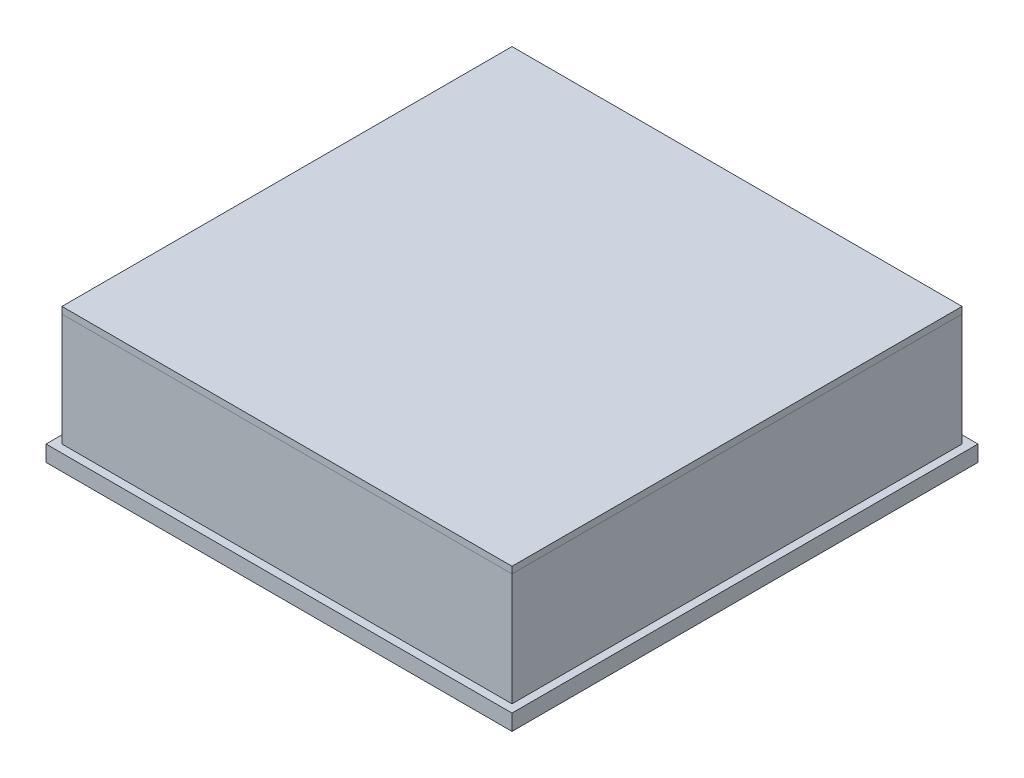
SolidWorks part; units mm, degrees
ref_plane "Front Plane" through (0, 0, 0) normal (0, 0, 1) x (1, 0, 0)
ref_plane "Top Plane" through (0, 0, 0) normal (0, 1, 0) x (1, 0, 0)
ref_plane "Right Plane" through (0, 0, 0) normal (1, 0, 0) x (0, 0, -1)
sketch "Sketch2" plane through (0, 0, 0) normal (0, 1, 0) x (1, 0, 0)
  line L0 (-4304.792, -4304.792) -> (-4304.792, 4304.792)
  line L1 (3999.992, -3999.992) -> (-3999.992, -3999.992)
  line L2 (3999.992, -3999.992) -> (3999.992, 3999.992)
  line L3 (3999.992, 3999.992) -> (-3999.992, 3999.992)
  line L4 (-3999.992, -3999.992) -> (-3999.992, 3999.992)
  line L5 (3999.992, -3999.992) -> (-3999.992, 3999.992) construction
  line L6 (3999.992, 3999.992) -> (-3999.992, -3999.992) construction
  line L7 (4304.792, 4304.792) -> (-4304.792, 4304.792)
  line L8 (4304.792, -4304.792) -> (4304.792, 4304.792)
  line L9 (4304.792, -4304.792) -> (-4304.792, -4304.792)
  point P0 (0, 0)
  dimension "D1" = 7999.984
  dimension "D2" = 7999.984
  dimension "D3" = 304.8
extrude "Boss-Extrude1" add sketch "Sketch2" along normal blind 1999.996
sketch "Sketch3" plane through (0, 0, 0) normal (0, -1, 0) x (1, 0, 0)
  line L0 (-4304.792, -4304.792) -> (-4304.792, 4304.792) construction
  line L1 (-4304.792, -4304.792) -> (-4304.792, 4304.792)
  line L2 (4304.792, -4304.792) -> (-4304.792, -4304.792) construction
  line L3 (4304.792, 4304.792) -> (4304.792, -4304.792) construction
  line L4 (-4304.792, 4304.792) -> (4304.792, 4304.792) construction
  line L5 (4304.792, -4304.792) -> (-4304.792, -4304.792)
  line L6 (4304.792, 4304.792) -> (4304.792, -4304.792)
  line L7 (-4304.792, 4304.792) -> (4304.792, 4304.792)
extrude "Boss-Extrude2" add sketch "Sketch3" along normal blind 152.4
sketch "Sketch4" plane through (0, -152.4, 0) normal (0, -1, 0) x (1, 0, 0)
  line L30 (-4457.192, 4457.192) -> (-4457.192, -4457.192)
  line L31 (-4457.192, -4457.192) -> (4457.192, -4457.192)
  line L32 (4457.192, -4457.192) -> (4457.192, 4457.192)
  line L33 (4457.192, 4457.192) -> (-4457.192, 4457.192)
  line L34 (-4457.192, 4457.192) -> (-4457.192, -4457.192)
  line L35 (-4457.192, -4457.192) -> (4457.192, -4457.192)
  line L36 (4457.192, -4457.192) -> (4457.192, 4457.192)
  line L37 (4457.192, 4457.192) -> (-4457.192, 4457.192)
  line L43 (3847.592, 3847.592) -> (-3847.592, 3847.592)
  line L44 (-3847.592, 3847.592) -> (-3847.592, -3847.592)
  line L45 (-3847.592, -3847.592) -> (3847.592, -3847.592)
  line L46 (3847.592, -3847.592) -> (3847.592, 3847.592)
  line L47 (3847.592, 3847.592) -> (-3847.592, 3847.592)
  line L48 (-3847.592, 3847.592) -> (-3847.592, -3847.592)
  line L49 (-3847.592, -3847.592) -> (3847.592, -3847.592)
  line L50 (3847.592, -3847.592) -> (3847.592, 3847.592)
  dimension "D1" = 152.4
  dimension "D2" = 152.4
extrude "Boss-Extrude3" add sketch "Sketch4" along normal blind 304.8
sketch "Sketch6" plane through (0, 0, 0) normal (0, 1, 0) x (1, 0, 0)
  line L0 (0, 0) -> (-3999.992, 3999.992) construction
  line L6 (-3999.992, 1656.8509) -> (-1656.8509, 1656.8509) construction
  line L7 (-3999.992, 3999.992) -> (-3999.992, -3999.992) construction
  line L19 (-1656.8509, 1656.8509) -> (-1656.8509, 3999.992) construction
  line L20 (3999.992, 3999.992) -> (-3999.992, 3999.992) construction
  line L22 (-1656.8509, 1656.8509) -> (0, 0) construction
  line L24 (1809.2509, 1504.4509) -> (1809.2509, 1809.2509)
  line L25 (-1504.4509, 1809.2509) -> (-1809.2509, 1809.2509)
  line L29 (-1504.4509, 1809.2509) -> (-1504.4509, 1504.4509)
  line L30 (-1504.4509, 1504.4509) -> (-1809.2509, 1504.4509)
  line L31 (-1809.2509, 1809.2509) -> (-1809.2509, 1504.4509)
  line L32 (-1504.4509, 1809.2509) -> (-1809.2509, 1504.4509) construction
  line L33 (-1504.4509, 1504.4509) -> (-1809.2509, 1809.2509) construction
  line L34 (1809.2509, 1809.2509) -> (1504.4509, 1809.2509)
  line L35 (1504.4509, 1504.4509) -> (1504.4509, 1809.2509)
  line L36 (1809.2509, 1504.4509) -> (1504.4509, 1504.4509)
  line L37 (1504.4509, -1809.2509) -> (1809.2509, -1809.2509)
  line L38 (1809.2509, -1809.2509) -> (1809.2509, -1504.4509)
  line L39 (1504.4509, -1504.4509) -> (1809.2509, -1504.4509)
  line L40 (1504.4509, -1809.2509) -> (1504.4509, -1504.4509)
  line L41 (-1809.2509, -1504.4509) -> (-1809.2509, -1809.2509)
  line L42 (-1809.2509, -1809.2509) -> (-1504.4509, -1809.2509)
  line L43 (-1504.4509, -1504.4509) -> (-1504.4509, -1809.2509)
  line L44 (-1809.2509, -1504.4509) -> (-1504.4509, -1504.4509)
  point P30 (0, 0)
  dimension "D1" = 304.8
extrude "Boss-Extrude5" add sketch "Sketch6" along normal up to surface (1999.996 mm away) contours L25 L31 L30 L29 | L36 L24 L34 L35 | L40 L37 L38 L39 | L44 L41 L42 L43 region at (1656.8509, 0, -1656.8509) region at (-1656.8509, 0, -1656.8509) region at (1656.8509, 0, 1656.8509) region at (-1656.8509, 0, 1656.8509) up to face at (0, 1999.996, 0)
sketch "Sketch7" plane through (0, 1999.996, 0) normal (0, 1, 0) x (1, 0, 0)
  line L1 (4304.792, -4304.792) -> (-4304.792, -4304.792)
  line L2 (4304.792, -4304.792) -> (4304.792, 4304.792)
  line L3 (4304.792, 4304.792) -> (-4304.792, 4304.792)
  line L4 (-4304.792, -4304.792) -> (-4304.792, 4304.792)
  line L5 (4304.792, -4304.792) -> (-4304.792, 4304.792) construction
  line L6 (4304.792, 4304.792) -> (-4304.792, -4304.792) construction
  point P0 (0, 0)
extrude "Boss-Extrude6" add sketch "Sketch7" along normal blind 127 separate body
sketch "Sketch8" plane through (0, 0, -1504.4509) normal (0, 0, 1) x (1, 0, 0)
  line L0 (-3999.992, 1999.996) -> (-3999.992, 0) construction
  line L1 (3999.992, 1999.996) -> (-3999.992, 1999.996)
  line L2 (3999.992, 1999.996) -> (3999.992, 1753.1524)
  line L3 (3999.992, 1753.1524) -> (-3999.992, 1753.1524)
  line L4 (-3999.992, 1999.996) -> (-3999.992, 1753.1524)
  line L5 (3999.992, 1999.996) -> (-3999.992, 1753.1524) construction
  line L6 (3999.992, 1753.1524) -> (-3999.992, 1999.996) construction
  line L7 (3999.992, 1999.996) -> (-3999.992, 1999.996) construction
  line L8 (3999.992, 1999.996) -> (-3999.992, 1999.996)
  point P0 (0, 1876.5742)
ref_axis "Axis1" through (0, 0, 0) along (0, 1, 0)
sketch "Right Plane Rebar" plane through (0, 0, 0) normal (1, 0, 0) x (0, 0, -1)
  line L0 (4234.942, 2063.496) -> (4234.942, -393.7)
  line L1 (-4457.192, -457.2) -> (4457.192, -457.2) construction
  line L2 (4069.842, 2044.446) -> (4069.842, 50.8)
  line L3 (4222.242, 1314.196) -> (4222.242, 1923.796)
  line L4 (-4304.792, 1999.996) -> (-4304.792, -152.4)
  line L5 (-4304.792, -152.4) -> (4304.792, -152.4)
  line L6 (4304.792, -152.4) -> (4304.792, 1999.996)
  line L7 (4304.792, 1999.996) -> (-4304.792, 1999.996)
  line L8 (-4304.792, 1999.996) -> (-4304.792, -152.4)
  line L9 (-4304.792, -152.4) -> (4304.792, -152.4)
  line L10 (4304.792, -152.4) -> (4304.792, 1999.996)
  line L12 (4095.242, 2050.796) -> (3485.642, 2050.796)
  line L13 (4095.242, 2063.496) -> (-4095.242, 2063.496)
  line L14 (0, 1351.4578) -> (0, -1351.4578) construction
  line L15 (3955.542, -88.9) -> (-3955.542, -88.9)
  line L16 (3999.992, 1999.996) -> (-3999.992, 1999.996)
  line L17 (3999.992, 1999.996) -> (-3999.992, 1999.996)
  line L18 (-4304.792, 2126.996) -> (4304.792, 2126.996) construction
  line L19 (3999.992, 0) -> (3999.992, 1999.996)
  line L20 (-3999.992, 0) -> (3999.992, 0)
  line L21 (-3999.992, 1999.996) -> (-3999.992, 0)
  line L27 (3999.992, 0) -> (3999.992, 1999.996)
  line L28 (-3999.992, 0) -> (3999.992, 0)
  line L29 (-3999.992, 1999.996) -> (-3999.992, 0)
  line L32 (4082.542, 660.4) -> (4082.542, 50.8)
  line L33 (3955.542, -76.2) -> (3345.942, -76.2)
  line L38 (4304.792, 1999.996) -> (-4304.792, 1999.996)
  arc A0 (4222.242, 1923.796) -> (4095.242, 2050.796) centre (4095.242, 1923.796) ccw
  arc A1 (3955.542, -76.2) -> (4082.542, 50.8) centre (3955.542, 50.8) ccw
  point P23 (4222.242, 2050.796)
  point P30 (0, 2063.496)
  point P41 (0, -88.9)
  dimension "D12" = 127
  dimension "D19" = 127
  dimension "D5" = 69.85
  dimension "Vertical Rebar Outer" = 2457.196
  dimension "D4" = 63.5
  dimension "D8" = 69.85
  dimension "D11" = 12.7
  dimension "D10" = 6.35
  dimension "D13" = 609.6
  dimension "D14" = 609.6
  dimension "D15" = 12.7
  dimension "D16" = 63.5
  dimension "D17" = 12.7
  dimension "D18" = 12.7
  dimension "D7" = 609.6
  dimension "D20" = 609.6
  dimension "Vertical Rebar Inner" = 1993.646
  dimension "Lid Rebar Length" = 8190.484
  dimension "Base Rebar Length" = 7911.084
  dimension "D3" = 63.5
  dimension "D6" = 63.5
sketch "Front Plane Rebar" plane through (0, 0, 0) normal (0, 0, 1) x (1, 0, 0)
  line L0 (4247.642, 2063.496) -> (4247.642, -393.7)
  line L1 (3999.992, 1999.996) -> (3999.992, 0) construction
  line L2 (4057.142, 2031.746) -> (4057.142, 63.5)
  line L3 (4234.942, 1301.496) -> (4234.942, 1911.096)
  line L4 (-4304.792, 2126.996) -> (4304.792, 2126.996) construction
  line L5 (4457.192, -457.2) -> (-4457.192, -457.2) construction
  line L6 (4457.192, -152.4) -> (-4457.192, -152.4) construction
  line L7 (4304.792, 2126.996) -> (-4304.792, 2126.996) construction
  line L8 (-4304.792, 1999.996) -> (-4304.792, -152.4)
  line L9 (-4304.792, -152.4) -> (4304.792, -152.4)
  line L10 (4304.792, -152.4) -> (4304.792, 1999.996)
  line L12 (4107.942, 2038.096) -> (3498.342, 2038.096)
  line L13 (4107.942, 2050.796) -> (-4107.942, 2050.796)
  line L15 (3942.842, -76.2) -> (-3942.842, -76.2)
  line L17 (3999.992, 1999.996) -> (-3999.992, 1999.996)
  line L19 (-3999.992, 0) -> (3999.992, 0)
  line L20 (3999.992, 0) -> (3999.992, 1999.996)
  line L21 (3999.992, 1999.996) -> (-3999.992, 1999.996)
  line L22 (-3999.992, 1999.996) -> (-3999.992, 0)
  line L23 (-3999.992, 0) -> (3999.992, 0)
  line L27 (3999.992, 0) -> (3999.992, 1999.996)
  line L28 (-3999.992, 0) -> (3999.992, 0)
  line L29 (-3999.992, 1999.996) -> (-3999.992, 0)
  line L32 (4069.842, 673.1) -> (4069.842, 63.5)
  line L33 (3942.842, -63.5) -> (3333.242, -63.5)
  line L34 (3999.992, 0) -> (3999.992, 1999.996)
  line L35 (3999.992, 1999.996) -> (-3999.992, 1999.996)
  line L36 (-3999.992, 1999.996) -> (-3999.992, 0)
  line L37 (4304.792, -152.4) -> (4304.792, 1999.996)
  line L38 (4304.792, 1999.996) -> (-4304.792, 1999.996)
  line L39 (-4304.792, -152.4) -> (4304.792, -152.4)
  line L40 (-4304.792, 1999.996) -> (-4304.792, -152.4)
  line L41 (4304.792, 1999.996) -> (-4304.792, 1999.996)
  line L42 (4304.792, -152.4) -> (4304.792, 1999.996)
  line L43 (-4304.792, -152.4) -> (4304.792, -152.4)
  line L44 (-4304.792, 1999.996) -> (-4304.792, -152.4)
  line L45 (4304.792, 1999.996) -> (-4304.792, 1999.996)
  arc A0 (4234.942, 1911.096) -> (4107.942, 2038.096) centre (4107.942, 1911.096) ccw
  arc A1 (3942.842, -63.5) -> (4069.842, 63.5) centre (3942.842, 63.5) ccw
  point P23 (4234.942, 2038.096)
  point P30 (0, 2050.796)
  point P41 (0, -76.2)
  dimension "D12" = 127
  dimension "D19" = 127
  dimension "Vertical Rebar Outer" = 2457.196
  dimension "D4" = 63.5
  dimension "D11" = 12.7
  dimension "D10" = 6.35
  dimension "D13" = 609.6
  dimension "D14" = 609.6
  dimension "D15" = 12.7
  dimension "D17" = 12.7
  dimension "D18" = 12.7
  dimension "D7" = 609.6
  dimension "D20" = 609.6
  dimension "D5" = 57.15
  dimension "D8" = 57.15
  dimension "D16" = 76.2
  dimension "Vertical Rebar Inner" = 1968.246
  dimension "Lid Rebar Length" = 8215.884
  dimension "Base Rebar Length" = 7885.684
  dimension "D3" = 76.2
  dimension "D21" = 63.5
sketch "Sketch9" plane through (0, -152.4, 0) normal (0, 1, 0) x (1, 0, 0)
  line L0 (-4260.342, 4393.692) -> (-4260.342, -4393.692)
  line L1 (-4457.192, -4457.192) -> (-4457.192, 4457.192) construction
  line L2 (-4457.192, -4457.192) -> (-4457.192, 4457.192)
  line L3 (-3847.592, -3847.592) -> (-3847.592, 3847.592) construction
  line L4 (-3847.592, -3847.592) -> (-3847.592, 3847.592)
  line L5 (-4457.192, 4457.192) -> (4457.192, 4457.192) construction
  line L6 (4457.192, -4457.192) -> (-4457.192, -4457.192) construction
  line L7 (-4044.442, 4152.392) -> (-4044.442, -4152.392)
  line L8 (4393.692, 4260.342) -> (-4393.692, 4260.342)
  line L9 (4152.392, 4044.442) -> (-4152.392, 4044.442)
  line L10 (4260.342, -4393.692) -> (4260.342, 4393.692)
  line L11 (4044.442, -4152.392) -> (4044.442, 4152.392)
  line L12 (-4393.692, -4260.342) -> (4393.692, -4260.342)
  line L13 (-4152.392, -4044.442) -> (4152.392, -4044.442)
  point P27 (0, 0)
  dimension "D3" = 63.5
  dimension "D1" = 196.85
  dimension "D2" = 63.5
  dimension "D4" = 196.85
  dimension "D5" = 304.8
  dimension "D6" = 304.8
  dimension "D7" = 8787.384
  dimension "D8" = 8304.784
  dimension "D9" = 4
sketch "Sketch11" plane through (0, 0, -1504.4509) normal (0, 0, 1) x (1, 0, 0)
  line L0 (-1745.7509, 2063.496) -> (-1745.7509, -88.9)
  line L1 (-1745.7509, 2063.496) -> (-1745.7509, 1930.146)
  line L2 (-4304.792, 2126.996) -> (4304.792, 2126.996) construction
  line L4 (4457.192, -152.4) -> (-4457.192, -152.4) construction
  line L5 (-1745.7509, -88.9) -> (-1745.7509, 44.45)
  line L6 (-1504.4509, 0) -> (-1504.4509, 1999.996)
  line L7 (-1504.4509, 1999.996) -> (-1809.2509, 1999.996)
  line L8 (-1809.2509, 1999.996) -> (-1809.2509, 0)
  line L9 (-1809.2509, 0) -> (-1504.4509, 0)
  line L10 (-1504.4509, 0) -> (-1504.4509, 1999.996)
  line L11 (-1504.4509, 1999.996) -> (-1809.2509, 1999.996)
  line L12 (-1809.2509, 1999.996) -> (-1809.2509, 0)
  line L13 (-1809.2509, 0) -> (-1504.4509, 0)
  dimension "D4" = 63.5
  dimension "D2" = 63.5
  dimension "D3" = 133.35
  dimension "D5" = 63.5
  dimension "D6" = 133.35
  dimension "D7" = 1885.696
sketch "Sketch13" plane through (0, 2126.996, 0) normal (0, 1, 0) x (1, 0, 0)
  line L0 (-4222.242, 4253.992) -> (-4222.242, -4253.992)
  line L1 (-4304.792, 4304.792) -> (-4304.792, -4304.792) construction
  line L2 (-4304.792, 4304.792) -> (4304.792, 4304.792) construction
  line L3 (4304.792, -4304.792) -> (-4304.792, -4304.792) construction
  dimension "D1" = 82.55
  dimension "D2" = 50.8
  dimension "D3" = 50.8
  dimension "D4" = 8507.984
equation "\"Rebar Diameter\"=0.5"
equation "\"Min Coverage\"=2.5"
equation "\"D5@Right Plane Rebar\" = \"Rebar Diameter\" / 2 + \"Min Coverage\""
equation "\"D4@Right Plane Rebar\" = \"Min Coverage\""
equation "\"D8@Right Plane Rebar\" = \"Min Coverage\" + \"Rebar Diameter\" / 2"
equation "\"Contact Length\"= 24"
equation "\"D11@Right Plane Rebar\" = \"Rebar Diameter\""
equation "\"Rebar Bend Radius\"= 5"
equation "\"D12@Right Plane Rebar\" = \"Rebar Bend Radius\""
equation "\"D10@Right Plane Rebar\" = \"Rebar Diameter\" / 2"
equation "\"D13@Right Plane Rebar\" = \"Contact Length\""
equation "\"D14@Right Plane Rebar\" = \"Contact Length\""
equation "\"D15@Right Plane Rebar\" = \"Rebar Diameter\""
equation "\"D16@Right Plane Rebar\" = \"Min Coverage\""
equation "\"D17@Right Plane Rebar\" = \"Rebar Diameter\""
equation "\"D18@Right Plane Rebar\" = \"Rebar Diameter\""
equation "\"D19@Right Plane Rebar\" = \"Rebar Bend Radius\""
equation "\"D7@Right Plane Rebar\" = \"Contact Length\""
equation "\"D20@Right Plane Rebar\" = \"Contact Length\""
equation "\"D3@Right Plane Rebar\" = \"Min Coverage\""
equation "\"D6@Right Plane Rebar\" = \"Min Coverage\""
equation "\"D3@Front Plane Rebar\" = \"Rebar Diameter\" + \"Min Coverage\""
equation "\"D4@Front Plane Rebar\" = \"Min Coverage\""
equation "\"D16@Front Plane Rebar\" = \"Min Coverage\" + \"Rebar Diameter\""
equation "\"D21@Front Plane Rebar\" = \"Min Coverage\""
equation "\"D1@Sketch9\"=7.75"
equation "\"D2@Sketch9\"=\"Min Coverage\""
equation "\"D3@Sketch9\"=\"Min Coverage\""
equation "\"D4@Sketch9\"=7.75"
equation "\"D4@Sketch11\"=\"Min Coverage\""
equation "\"D2@Sketch11\"=\"Min Coverage\""
